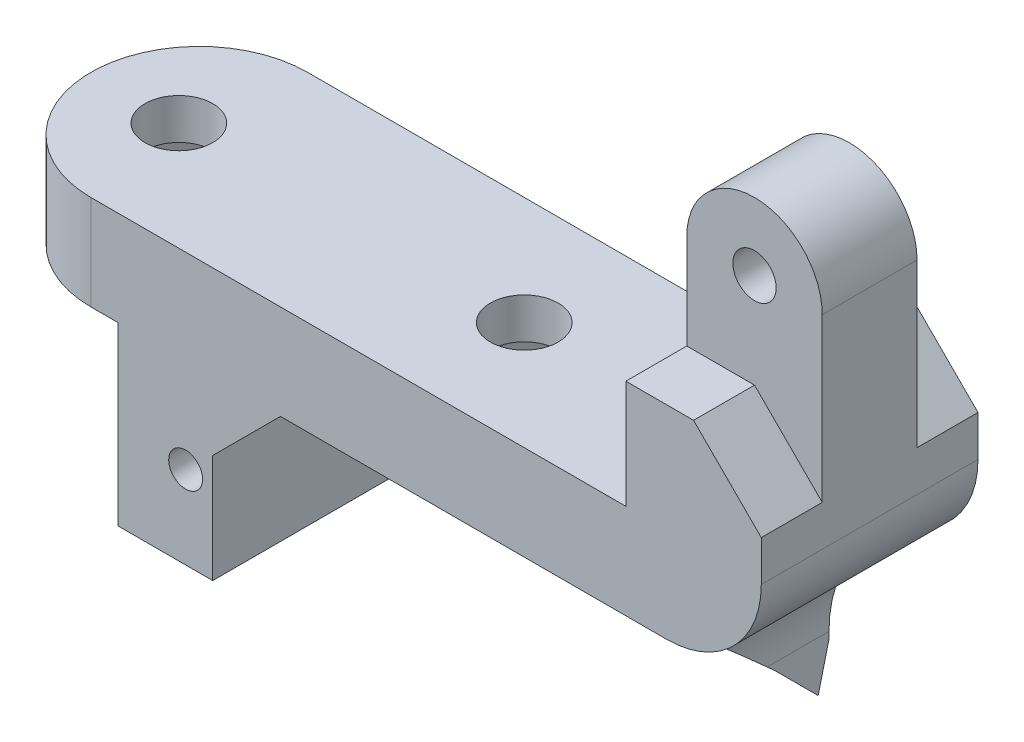
SolidWorks part; units mm, degrees
ref_plane "Plan de face" through (0, 0, 0) normal (0, 0, 1) x (1, 0, 0)
ref_plane "Plan de dessus" through (0, 0, 0) normal (0, 1, 0) x (1, 0, 0)
ref_plane "Plan de droite" through (0, 0, 0) normal (1, 0, 0) x (0, 0, -1)
sketch "Esquisse1" plane through (0, 0, 0) normal (0, 0, 1) x (1, 0, 0)
  line L0 (0, 0) -> (37.5, 0)
  line L1 (37.5, 0) -> (37.5, 20)
  line L2 (37.5, 20) -> (47.5, 20)
  line L3 (0, 0) -> (0, -20)
  line L4 (0, -20) -> (7, -20)
  line L5 (7, -20) -> (7, -7)
  line L6 (7, -7) -> (30.5, -7)
  line L7 (30.5, -7) -> (30.5, -20)
  line L8 (30.5, -20) -> (37.5, -20)
  line L9 (37.5, -20) -> (37.5, -7)
  line L10 (37.5, -7) -> (47.5, -7)
  line L11 (47.5, -7) -> (47.5, 20)
  line L12 (5, -13.9) -> (32.5, -13.9) construction
  line L13 (18.75, -13.9) -> (18.75, -7) construction
  circle A0 centre (5, -13.9) radius 1.25
  circle A1 centre (32.5, -13.9) radius 1.25
  dimension "D8" = 2.5
  dimension "D1" = 13
  dimension "D2" = 7
  dimension "D3" = 7
  dimension "D4" = 23.5
  dimension "D5" = 10
  dimension "D6" = 10
  dimension "D7" = 20
  dimension "D9" = 6.1
  dimension "D10" = 27.5
extrude "Boss.-Extru.1" add sketch "Esquisse1" along normal blind 16
sketch "Esquisse5" plane through (0, 20, 0) normal (0, 1, 0) x (1, 0, 0)
  line L0 (37.5, -16) -> (37.5, 0) construction
  line L1 (47.5, 0) -> (37.5, 0)
  line L2 (47.5, 0) -> (47.5, -4.5)
  line L3 (47.5, -4.5) -> (37.5, -4.5)
  line L4 (37.5, 0) -> (37.5, -4.5)
  line L6 (47.5, -16) -> (37.5, -16)
  line L7 (47.5, -16) -> (47.5, -11.5)
  line L8 (47.5, -11.5) -> (37.5, -11.5)
  line L9 (37.5, -16) -> (37.5, -11.5)
  dimension "D1" = 7
extrude "Enlèv. mat.-Extru.3" cut sketch "Esquisse5" against normal blind 12
sketch "Esquisse6" plane through (0, 0, 11.5) normal (0, 0, 1) x (1, 0, 0)
  line L0 (37.5, 15) -> (35.4995, 15)
  line L1 (35.4995, 15) -> (35.4995, 22.0005)
  line L2 (35.4995, 22.0005) -> (49.5005, 22.0005)
  line L4 (37.5, 8) -> (37.5, 20) construction
  line L5 (47.5, 8) -> (47.5, 20) construction
  line L6 (47.5, 20) -> (37.5, 20) construction
  line L7 (47.5, 15) -> (49.5005, 15)
  line L8 (49.5005, 15) -> (49.5005, 22.0005)
  line L9 (42.5, 20) -> (42.5, 22.0005) construction
  circle A0 centre (42.5, 15) radius 1.6
  circle A1 centre (42.5, 15) radius 5 construction
  arc A2 (37.5, 15) -> (47.5, 15) centre (42.5, 15) cw
  dimension "D1" = 3.2
  dimension "D2" = 2.0005
extrude "Enlèv. mat.-Extru.4" cut sketch "Esquisse6" against normal through all contours L2 L8 L7 A2 L0 L1 | A0
sketch "Esquisse10" plane through (0, 0, 0) normal (0, 0, -1) x (-1, 0, 0)
  line L1 (-7, -7) -> (0, -7)
  line L2 (-7, -7) -> (-7, -20)
  line L3 (-7, -20) -> (0, -20)
  line L4 (0, -7) -> (0, -20)
  line L5 (-30.5, -7) -> (-37.5, -7)
  line L6 (-30.5, -7) -> (-30.5, -20)
  line L7 (-30.5, -20) -> (-37.5, -20)
  line L8 (-37.5, -7) -> (-37.5, -20)
extrude "Enlèv. mat.-Extru.5" cut sketch "Esquisse10" against normal blind 1
sketch "Esquisse11" plane through (0, -20, 0) normal (0, -1, 0) x (1, 0, 0)
  line L0 (37.5, 16) -> (37.5, 1) construction
  line L1 (30.5, 16) -> (37.5, 16)
  line L2 (30.5, 16) -> (30.5, 5)
  line L3 (30.5, 5) -> (37.5, 5)
  line L4 (37.5, 16) -> (37.5, 5)
  line L5 (37.5, 1) -> (30.5, 1) construction
  dimension "D1" = 4
extrude "Enlèv. mat.-Extru.6" cut sketch "Esquisse11" against normal up to surface (13 mm away) up to face at (24.5, -7, 6.8)
fillet "Congé6" radius 7 1 edges at (47.5, -7, 8)
fillet "Congé5" radius 10 1 edges at (37.5, -7, 3)
chamfer "Chanfrein2" distance 1 angle 76 1 edges at (34, -20, 1) first distance on face at (34, -20, 3)
chamfer "Chanfrein3" distance 10 angle 42 2 edges at (35.5, -7, 5) (41.9742, -6.843, 5) first distance on face at (23.7, -7, 4.6) first distance on face at (43.3413, -5.4956, 5.5)
sketch "Esquisse12" plane through (0, 0, 16) normal (0, 0, 1) x (1, 0, 0)
  line L0 (7, -12) -> (7, -7)
  line L1 (7, -20) -> (7, -7) construction
  line L2 (7, -7) -> (12, -7)
  line L3 (7, -7) -> (40.5, -7) construction
  line L4 (12, -7) -> (7, -12)
  dimension "D1" = 5
extrude "Boss.-Extru.5" add sketch "Esquisse12" against normal blind 9
ref_plane "Plan1" through (0, 0, 8) normal (0, 0, -1) x (-1, 0, 0)
sketch "Esquisse13" plane through (0, 0, 8) normal (0, 0, -1) x (-1, 0, 0)
  line L0 (-19.5, 0) -> (-19.5, -5.5)
  line L1 (-19.5, -5.5) -> (-18, -7)
  line L2 (-18, -7) -> (-18, -12)
  line L3 (-18, -12) -> (-22, -12)
  line L4 (-22, -12) -> (-22, 0)
  line L5 (-22, 0) -> (-19.5, 0)
  line L6 (-37.5, 0) -> (0, 0) construction
  line L7 (-18, -7) -> (-22, -7) construction
  point P8 (-12, -7)
  dimension "D1" = 5
  dimension "D2" = 2.5
  dimension "D3" = 1.5
  dimension "D4" = 1.5
  dimension "D5" = 15
revolve "Enlèvement de matière-Révolution1" cut sketch "Esquisse13" angle 360 about L4
sketch "Esquisse14" plane through (0, 0, 0) normal (0, 1, 0) x (1, 0, 0)
  line L2 (0, -16) -> (-2, -16)
  line L3 (0, -16) -> (0, 0)
  line L4 (0, 0) -> (-2, 0)
  line L5 (-2, -16) -> (-2, 0) construction
  arc A0 (-2, -16) -> (-2, 0) centre (-2, -8) cw
  dimension "D1" = 2
extrude "Boss.-Extru.6" add sketch "Esquisse14" against normal up to surface (7 mm away) up to face at (22, -7, 4)
pattern_linear "Répétition linéaire1" count 2 spacing 25.5 along (-1, 0, 0) of "Enlèvement de matière-Révolution1"
sketch "Esquisse15" plane through (0, -7, 0) normal (0, -1, 0) x (1, 0, 0)
  line L0 (17.208, 8) -> (19.604, 12.15)
  line L1 (19.604, 12.15) -> (24.396, 12.15)
  line L2 (24.396, 12.15) -> (26.792, 8)
  line L3 (26.792, 8) -> (24.396, 3.85)
  line L4 (24.396, 3.85) -> (19.604, 3.85)
  line L5 (19.604, 3.85) -> (17.208, 8)
  circle A0 centre (22, 8) radius 4.792 construction
  dimension "D1" = 8.3
extrude "Enlèv. mat.-Extru.7" cut sketch "Esquisse15" against normal blind 4 and the other way through all
pattern_linear "Répétition linéaire2" count 2 spacing 25.5 along (-1, 0, 0) of "Enlèv. mat.-Extru.7"
sketch "Esquisse16" plane through (30.5, 0, 0) normal (-1, 0, 0) x (0, 0, 1)
  line L0 (5, -16.004) -> (1, -20)
  line L1 (5, -20) -> (1, -20)
  line L2 (5, -20) -> (5, -16.004)
  line L5 (1, -15.9892) -> (1, -20) construction
extrude "Enlèv. mat.-Extru.8" cut sketch "Esquisse16" against normal through all
chamfer "Chamfer1" distance 5 angle 45 2 edges at (47.5, 8, 13.75) (47.5, 8, 2.25)
